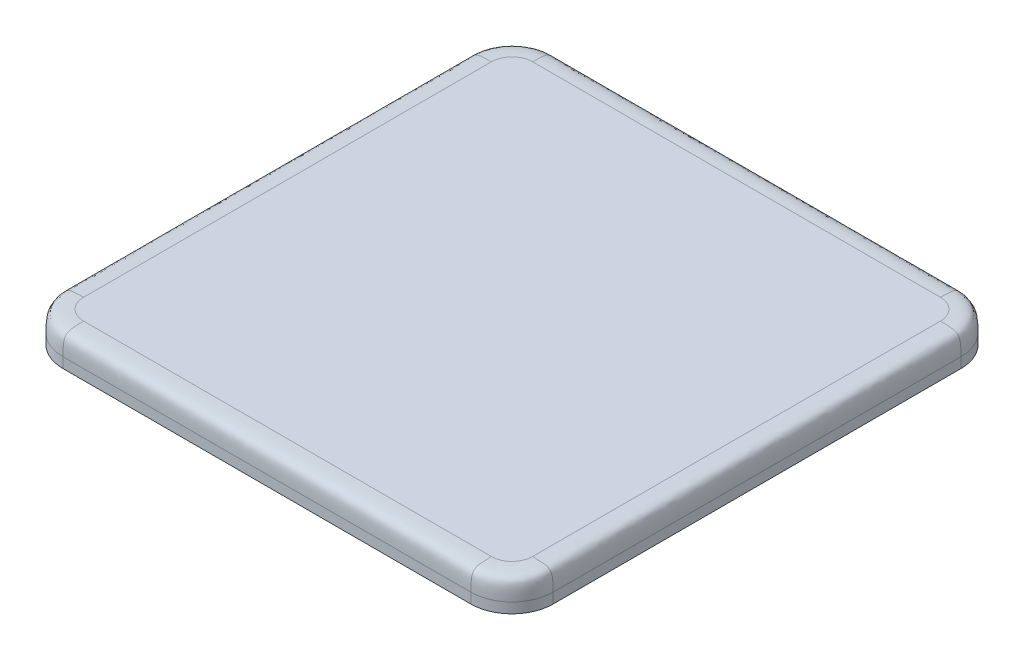
SolidWorks part; units mm, degrees
ref_plane "Front" through (0, 0, 0) normal (0, 0, 1) x (1, 0, 0)
ref_plane "Top" through (0, 0, 0) normal (0, 1, 0) x (1, 0, 0)
ref_plane "Right" through (0, 0, 0) normal (1, 0, 0) x (0, 0, -1)
sketch "Sketch1" plane through (0, 0, 0) normal (0, 0, 1) x (1, 0, 0)
  line L1 (-7.5629, 0) -> (7.5629, 0)
  line L2 (-7.5629, 0) -> (-7.5629, 0.9525)
  line L3 (-7.5629, 0.9525) -> (7.5629, 0.9525)
  line L4 (7.5629, 0) -> (7.5629, 0.9525)
  line L5 (0, 0.9525) -> (0, 0) construction
  line L6 (-7.5629, 0.4763) -> (7.5629, 0.4763) construction
  point P216 (0, 0.4763)
  dimension "D1" = 15.1257
  dimension "D2" = 0.9525
extrude "Boss-Extrude1" add sketch "Sketch1" along normal blind 15.1257
fillet "Fillet3" radius 1.27 4 edges at (-7.5629, 0.4763, 0) (-7.5629, 0.4763, 15.1257) (7.5629, 0.4763, 15.1257) (7.5629, 0.4763, 0)
fillet "Fillet1" radius 0.635 8 edges at (7.5629, 0.9525, 7.5629) (0, 0.9525, 15.1257) (-7.5629, 0.9525, 7.5629) (0, 0.9525, 0) (7.1909, 0.9525, 0.372) (7.1909, 0.9525, 14.7537) (-7.1909, 0.9525, 14.7537) (-7.1909, 0.9525, 0.372)
